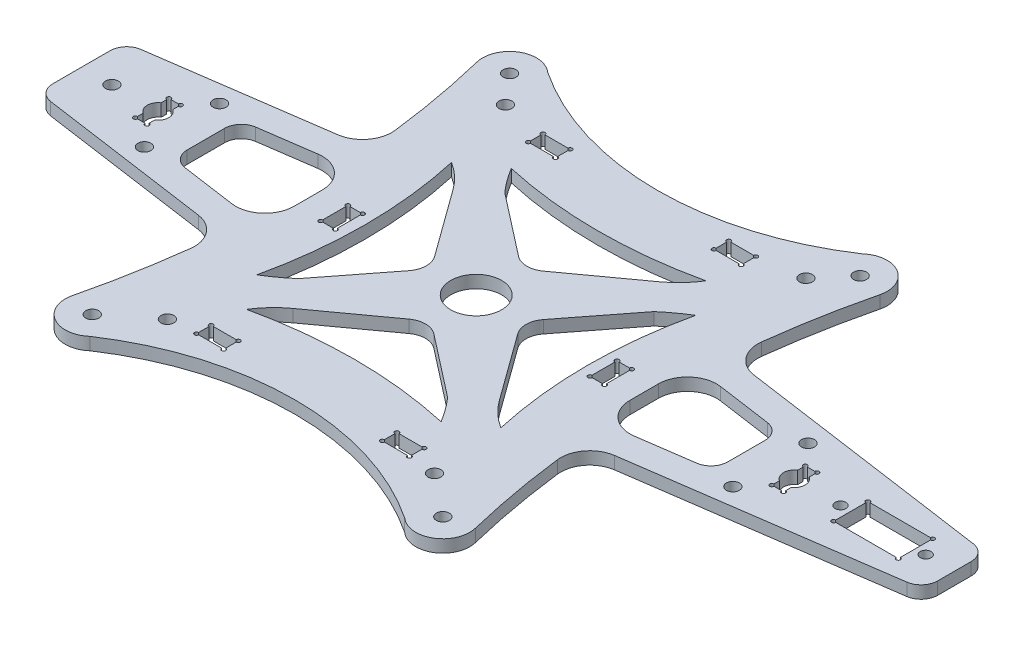
SolidWorks part; units mm, degrees
material "PPS"
ref_plane "前视基准面" through (0, 0, 0) normal (0, 0, 1) x (1, 0, 0)
ref_plane "上视基准面" through (0, 0, 0) normal (0, 1, 0) x (1, 0, 0)
ref_plane "右视基准面" through (0, 0, 0) normal (1, 0, 0) x (0, 0, -1)
sketch "草图1" plane through (0, 0, 0) normal (0, 1, 0) x (1, 0, 0)
  line L3 (-133.7177, 0) -> (146.3754, 0) construction
  line L56 (0, 96.0639) -> (0, -115.1457) construction
  line L65 (-25.5, 41.5) -> (-19, 41.5)
  line L66 (-34, 3.25) -> (-30.5, 3.25)
  line L70 (-34, 3.25) -> (-34, -3.25)
  line L76 (-34, -3.25) -> (-30.5, -3.25)
  line L80 (-30.5, 3.25) -> (-30.5, -3.25)
  line L81 (-25.5, -38) -> (-19, -38)
  line L82 (-25.5, -38) -> (-25.5, -41.5)
  line L83 (-25.5, -41.5) -> (-19, -41.5)
  line L84 (-19, -38) -> (-19, -41.5)
  line L85 (-19, 38) -> (-19, 41.5)
  line L86 (-25.5, 38) -> (-19, 38)
  line L142 (-25.5, 38) -> (-25.5, 41.5)
  line L143 (25.5, 38) -> (25.5, 41.5)
  line L144 (25.5, 38) -> (19, 38)
  line L145 (19, 38) -> (19, 41.5)
  line L146 (19, -38) -> (19, -41.5)
  line L147 (25.5, -41.5) -> (19, -41.5)
  line L148 (25.5, -38) -> (25.5, -41.5)
  line L149 (25.5, -38) -> (19, -38)
  line L150 (30.5, 3.25) -> (30.5, -3.25)
  line L151 (34, -3.25) -> (30.5, -3.25)
  line L152 (34, 3.25) -> (34, -3.25)
  line L153 (34, 3.25) -> (30.5, 3.25)
  line L154 (25.5, 41.5) -> (19, 41.5)
  line L155 (77.65, -2.1518) -> (77.65, -4)
  line L156 (74.85, 4) -> (77.65, 4)
  line L157 (74.85, 4) -> (74.85, 2.1768)
  line L158 (74.85, -4) -> (77.65, -4)
  line L159 (77.65, 4) -> (77.65, 2.1518)
  line L160 (74.85, -2.1768) -> (74.85, -4)
  line L161 (97.5, 7.6653) -> (97.5, -9.1503) construction
  line L162 (89.75, 4.1) -> (105.25, 4.1)
  line L163 (89.75, 4.1) -> (89.75, -4.1)
  line L164 (89.75, -4.1) -> (105.25, -4.1)
  line L165 (105.25, 4.1) -> (105.25, -4.1)
  line L166 (-97.5, 7.6653) -> (-97.5, -9.1503) construction
  line L171 (-74.85, -2.1768) -> (-74.85, -4)
  line L172 (-77.65, 4) -> (-77.65, 2.1518)
  line L173 (-74.85, -4) -> (-77.65, -4)
  line L174 (-74.85, 4) -> (-74.85, 2.1768)
  line L175 (-74.85, 4) -> (-77.65, 4)
  line L176 (-77.65, -2.1518) -> (-77.65, -4)
  line L177 (114.5911, 7.4683) -> (114.5911, -7.4683)
  line L178 (114.5911, 7.4683) -> (43.1936, 17.6463)
  line L179 (114.5911, -7.4683) -> (43.1936, -17.6463)
  line L183 (-24.7128, 19.184) -> (-10.803, 0)
  line L184 (19.184, 24.7128) -> (0, 10.803)
  line L185 (-24.7128, -17.8765) -> (-10.803, 0)
  line L186 (-17.8765, 24.7128) -> (0, 10.803)
  line L187 (24.7128, -19.184) -> (10.803, 0)
  line L188 (24.7128, 17.8765) -> (10.803, 0)
  line L189 (-19.184, -24.7128) -> (0, -10.803)
  line L190 (17.8765, -24.7128) -> (0, -10.803)
  line L191 (-94.5795, 10.321) -> (-94.5795, -10.321)
  line L192 (-43.1936, 17.6463) -> (-94.5795, 10.321)
  line L193 (-94.5795, -10.321) -> (-43.1936, -17.6463)
  line L195 (-64.75, -7.9571) -> (-64.75, 7.9571)
  line L196 (-64.75, 7.9571) -> (-40.25, 11.4497)
  line L197 (-40.25, 11.4497) -> (-40.25, -11.4497)
  line L198 (-64.75, -7.9571) -> (-40.25, -11.4497)
  line L199 (64.75, 7.9571) -> (40.25, 11.4497)
  line L200 (40.25, 11.4497) -> (40.25, -11.4497)
  line L201 (64.75, -7.9571) -> (40.25, -11.4497)
  line L202 (64.75, 7.9571) -> (64.75, -7.9571)
  circle A0 centre (-36, 43) radius 1.55
  circle A1 centre (-32, -42) radius 1.55
  circle A2 centre (32, -42) radius 1.55
  circle A3 centre (36, 43) radius 1.55
  circle A4 centre (42, 50) radius 1.55
  circle A5 centre (42, -50) radius 1.55
  circle A6 centre (-42, -50) radius 1.55
  circle A7 centre (-42, 50) radius 1.55
  arc A8 (74.85, 2.1768) -> (74.85, -2.1768) centre (76.2307, 0) ccw
  arc A9 (77.65, -2.1518) -> (77.65, 2.1518) centre (76.2307, 0) ccw
  circle A10 centre (107.7, 0) radius 1.3
  circle A11 centre (87.3, 0) radius 1.3
  circle A12 centre (-87.3, 0) radius 1.3 construction
  arc A14 (-77.65, -2.1518) -> (-77.65, 2.1518) centre (-76.2307, 0) cw
  arc A15 (-74.85, 2.1768) -> (-74.85, -2.1768) centre (-76.2307, 0) cw
  arc A18 (-37.7098, 54.831) -> (37.7098, 54.831) centre (0, 111.5317) ccw
  arc A20 (48.2756, 48.4632) -> (43.1936, 17.6463) centre (246.1791, 0) ccw
  arc A21 (48.2756, 48.4632) -> (37.7098, 54.831) centre (42, 50) ccw
  arc A22 (-37.7098, -54.831) -> (37.7098, -54.831) centre (0, -111.5317) cw
  arc A23 (48.2756, -48.4632) -> (43.1936, -17.6463) centre (246.1791, 0) cw
  arc A24 (48.2756, -48.4632) -> (37.7098, -54.831) centre (42, -50) cw
  arc A26 (-48.2756, -48.4632) -> (-37.7098, -54.831) centre (-42, -50) ccw
  arc A27 (-48.2756, -48.4632) -> (-43.1936, -17.6463) centre (-246.1791, 0) ccw
  arc A28 (-48.2756, 48.4632) -> (-37.7098, 54.831) centre (-42, 50) cw
  arc A30 (-48.2756, 48.4632) -> (-43.1936, 17.6463) centre (-246.1791, 0) cw
  arc A31 (-24.7128, 19.184) -> (-30.4857, 24.5725) centre (-41.4252, 7.0662) ccw
  arc A32 (-24.7128, -17.8765) -> (-30.4857, -22.0817) centre (-52.1779, 13.7617) cw
  arc A33 (-30.4857, -22.0817) -> (-30.4857, 24.5725) centre (-134.387, 1.2454) ccw
  arc A34 (-17.8765, 24.7128) -> (-22.0817, 30.4857) centre (13.7617, 52.1779) cw
  arc A35 (-22.0817, 30.4857) -> (24.5725, 30.4857) centre (1.2454, 134.387) ccw
  arc A36 (19.184, 24.7128) -> (24.5725, 30.4857) centre (7.0662, 41.4252) ccw
  arc A37 (24.7128, 17.8765) -> (30.4857, 22.0817) centre (52.1779, -13.7617) cw
  arc A38 (30.4857, 22.0817) -> (30.4857, -24.5725) centre (134.387, -1.2454) ccw
  arc A39 (24.7128, -19.184) -> (30.4857, -24.5725) centre (41.4252, -7.0662) ccw
  arc A40 (17.8765, -24.7128) -> (22.0817, -30.4857) centre (-13.7617, -52.1779) cw
  arc A41 (22.0817, -30.4857) -> (-24.5725, -30.4857) centre (-1.2454, -134.387) ccw
  arc A42 (-19.184, -24.7128) -> (-24.5725, -30.4857) centre (-7.0662, -41.4252) ccw
  circle A43 centre (70.5, 9) radius 1.55
  circle A44 centre (70.5, -9) radius 1.55
  circle A45 centre (-70.5, -9) radius 1.55
  circle A46 centre (-70.5, 9) radius 1.55
  circle A47 centre (-87.3, 0) radius 1.55
  point P81 (-34, 0)
  point P118 (0, 0)
  point P140 (-40.25, 0)
  point P148 (0, 0)
  point P149 (-64.75, 0)
  point P150 (0, 0)
  point P151 (0, 0)
  point P152 (0, 0)
  point P153 (0, 0)
  point P154 (0, 0)
  point P155 (0, 0)
  point P156 (0, 0)
  point P157 (0, 0)
  point P158 (-12.8338, 0)
  point P159 (0, 0)
  point P160 (0, 0)
  point P161 (24.7128, 30.4857)
  dimension "D5" = 38
  dimension "D18" = 8.2
  dimension "D24" = 3.1
  dimension "D6" = 3.1
  dimension "D11" = 50
  dimension "D15" = 74.85
  dimension "D16" = 2.6
  dimension "D17" = 15.5
  dimension "D21" = 3.1
  dimension "D1" = 6.5
  dimension "D2" = 3.5
  dimension "D3" = 30.5
  dimension "D4" = 19
  dimension "D7" = 32
  dimension "D8" = 42
  dimension "D9" = 43
  dimension "D10" = 36
  dimension "D12" = 42
  dimension "D13" = 2.8
  dimension "D14" = 4
  dimension "D19" = 2.45
  dimension "D20" = 97.5
  dimension "D22" = 9
  dimension "D23" = 70.5
  dimension "D25" = 6.55
  dimension "D26" = 5.75
  dimension "D27" = 6.25
  dimension "D28" = 4
extrude "凸台-拉伸1" add sketch "草图1" along normal blind 3
fillet "圆角1" radius 4 8 edges at (114.5911, 1.5, -7.4683) (114.5911, 1.5, 7.4683) (-94.5795, 1.5, 10.321) (-94.5795, 1.5, -10.321) (-64.75, 1.5, 7.9571) (-64.75, 1.5, -7.9571) (64.75, 1.5, 7.9571) (64.75, 1.5, -7.9571)
fillet "圆角2" radius 7 8 edges at (43.1936, 1.5, -17.6463) (43.1936, 1.5, 17.6463) (-43.1936, 1.5, 17.6463) (-43.1936, 1.5, -17.6463) (40.25, 1.5, 11.4497) (40.25, 1.5, -11.4497) (-40.25, 1.5, 11.4497) (-40.25, 1.5, -11.4497)
sketch "草图2" plane through (0, 3, 0) normal (0, 1, 0) x (1, 0, 0)
  line L0 (0, 0) -> (0, -66.7571) construction
  circle A0 centre (-77.65, 4) radius 0.5
  circle A1 centre (-74.85, 4) radius 0.5
  circle A2 centre (-77.65, -4) radius 0.5
  circle A3 centre (-74.85, -4) radius 0.5
  circle A4 centre (-25.5, 41.5) radius 0.5
  circle A5 centre (-19, 41.5) radius 0.5
  circle A6 centre (-25.5, 38) radius 0.5
  circle A7 centre (-19, 38) radius 0.5
  circle A8 centre (-34, 3.25) radius 0.5
  circle A9 centre (-30.5, 3.25) radius 0.5
  circle A10 centre (-34, -3.25) radius 0.5
  circle A11 centre (-30.5, -3.25) radius 0.5
  circle A12 centre (-25.5, -38) radius 0.5
  circle A13 centre (-19, -38) radius 0.5
  circle A14 centre (-25.5, -41.5) radius 0.5
  circle A15 centre (-19, -41.5) radius 0.5
  circle A16 centre (19, -41.5) radius 0.5
  circle A17 centre (25.5, -41.5) radius 0.5
  circle A18 centre (19, -38) radius 0.5
  circle A19 centre (25.5, -38) radius 0.5
  circle A20 centre (30.5, -3.25) radius 0.5
  circle A21 centre (34, -3.25) radius 0.5
  circle A22 centre (30.5, 3.25) radius 0.5
  circle A23 centre (34, 3.25) radius 0.5
  circle A24 centre (19, 38) radius 0.5
  circle A25 centre (25.5, 38) radius 0.5
  circle A26 centre (19, 41.5) radius 0.5
  circle A27 centre (25.5, 41.5) radius 0.5
  circle A28 centre (74.85, -4) radius 0.5
  circle A29 centre (77.65, -4) radius 0.5
  circle A30 centre (74.85, 4) radius 0.5
  circle A31 centre (77.65, 4) radius 0.5
  circle A32 centre (89.75, 4.1) radius 0.5
  circle A33 centre (105.25, 4.1) radius 0.5
  circle A34 centre (89.75, -4.1) radius 0.5
  circle A35 centre (105.25, -4.1) radius 0.5
  dimension "D1" = 1
extrude "直角约束" cut sketch "草图2" against normal through all
sketch "草图3" plane through (0, 0, 0) normal (0, 1, 0) x (1, 0, 0)
  circle A0 centre (0, 0) radius 6.1
  dimension "D1" = 12.2
extrude "切除-拉伸2" cut sketch "草图3" along normal through all
fillet "圆角3" radius 5 4 edges at (0, 1.5, 10.803) (10.803, 1.5, 0) (0, 1.5, -10.803) (-10.803, 1.5, 0)
